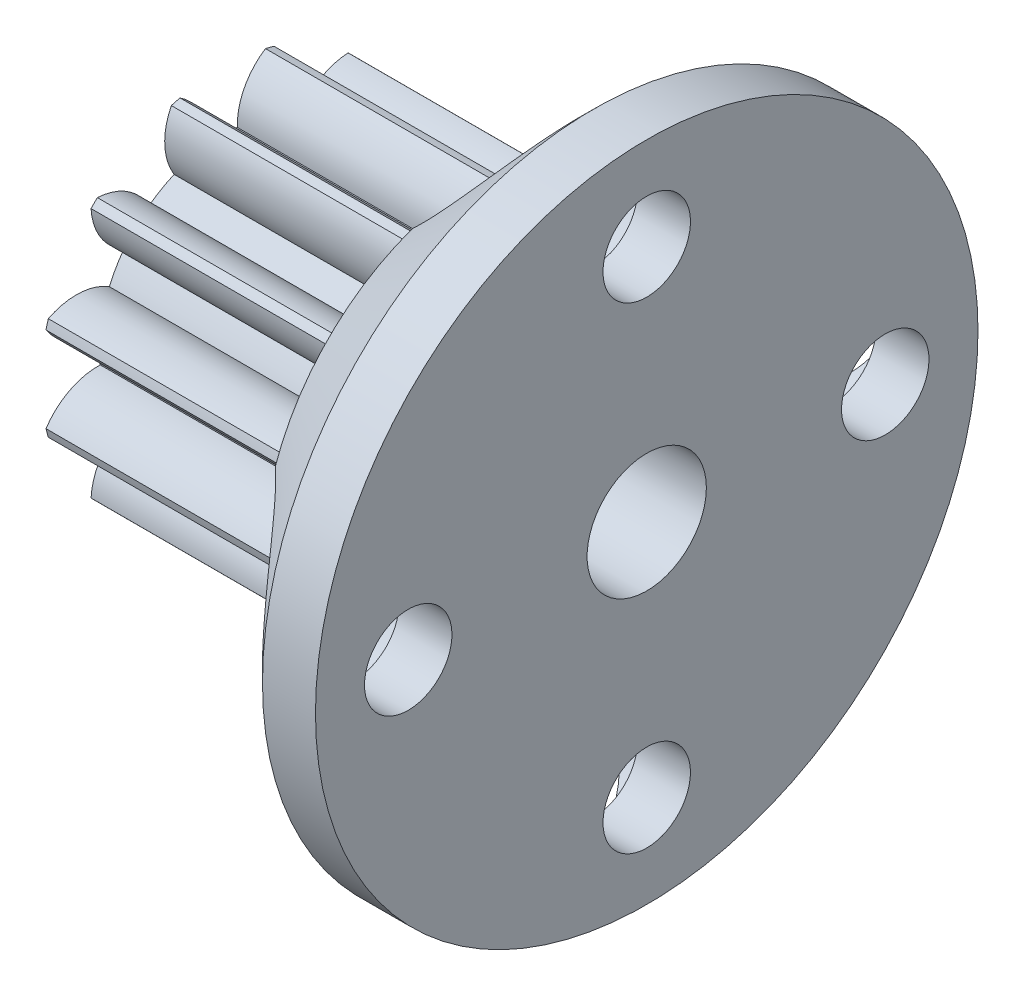
SolidWorks part; units mm, degrees
ref_plane "Plane1" through (0, 0, 0) normal (0, 0, 1) x (1, 0, 0)
ref_plane "Plane2" through (0, 0, 0) normal (0, 1, 0) x (1, 0, 0)
ref_plane "Plane3" through (0, 0, 0) normal (1, 0, 0) x (0, 0, -1)
other "Configuration Table"
sketch "HoldingSke" plane through (0, 0, 0) normal (0, 1, 0) x (1, 0, 0)
  line L0 (0, 0) -> (0.9981, -0.2122)
  line L1 (-15, 0) -> (100, 0) construction
  line L2 (0, 0) -> (-2.1039, 2.3779)
  line L3 (0, 0) -> (-11.863, 4.5341)
  line L4 (0, 0) -> (8.4473, 1.7955)
  line L5 (0, 0) -> (-46.8476, -17.4728)
  line L6 (0, 0) -> (-8.2896, -5.593)
  line L7 (-2.1039, 2.3779) -> (8.6586, 51.2059)
  line L8 (-76.2, 54.61) -> (-75.5, 54.61)
  line L9 (-71.009, 38.7566) -> (-53.1078, 45.2721)
  line L10 (-76.2, 71.12) -> (104.1128, 71.12)
  line L11 (0, 0) -> (-10, 0)
  line L12 (-76.2, 101.6) -> (-76.162, 101.6)
  line L13 (24.9733, 27.94) -> (52.9518, 28.4284)
  line L14 (24.9733, 27.94) -> (24.9743, 27.94)
  line L15 (24.9733, 27.94) -> (100.4006, 29.5858)
  line L16 (-63.627, -0.98) -> (-12.827, -0.98)
  circle A0 centre (0, 0) radius 1
  circle A1 centre (0, 0) radius 4.654
  circle A2 centre (0, 0) radius 37.5
  circle A3 centre (0, 0) radius 1
  dimension "Num_teeth" = 12
  dimension "Pitch_radius" = 180.3128
  dimension "Width" = 10
  dimension "Thickness" = 10
sketch "BasProSke" plane through (0, 0, 0) normal (0, 1, 0) x (1, 0, 0)
  line L0 (-10, 0) -> (60, 0) construction
  line L1 (0, 0) -> (0, 6.86)
  line L2 (0, 0) -> (10, 0)
  line L3 (10, 0) -> (10, 6.86)
  line L4 (10, 6.86) -> (0, 6.86)
  dimension "Thickness" = 10
  dimension "Diameter" = 13.72
revolve "Base-Revolve" add sketch "BasProSke" angle 360 about L0
sketch "TooCutSke" plane through (0, 0, 0) normal (1, 0, 0) x (0, 0, -1)
  line L1 (0, 0) -> (0, 107) construction
  line L2 (0, 0) -> (-0.8339, 5.8206) construction
  line L3 (0, 0) -> (-3.022, 11.2783) construction
  line L4 (-0.8339, 5.8206) -> (-1.511, 5.6391) construction
  arc A0 (0.552, 4.6211) -> (-0.552, 4.6211) centre (0, 0) ccw
  arc A1 (1.6415, 6.6869) -> (-1.6415, 6.6869) centre (0, 0) ccw
  circle A2 centre (0, 0) radius 5.88 construction
  circle A3 centre (0, 0) radius 5.5254 construction
  arc A4 (-0.552, 4.6211) -> (-1.6415, 6.6869) centre (-2.9026, 4.7016) ccw
  arc A5 (1.6415, 6.6869) -> (0.552, 4.6211) centre (2.9026, 4.7016) ccw
extrude "ToothCut" cut sketch "TooCutSke" along normal through all
fillet "Breaks" [suppressed] radius 0.0196 tangent propagation no
fillet "RootFillets" [suppressed] radius 0.246
pattern_circular "TeethCuts" count 12 every 30 about axis through (-10, 0, 0) along (1, 0, 0) of "ToothCut", "RootFillets", "Breaks"
sketch "HubNeaOneSke" plane through (0, 0, 0) normal (-1, 0, 0) x (0, 0, 1)
  circle A0 centre (0, 0) radius 4.654
  dimension "Diameter" = 9.308
extrude "HubNearOne" [suppressed] add sketch "HubNeaOneSke" along normal blind 40.0001
sketch "HubNeaBotSke" plane through (0, 0, 0) normal (-1, 0, 0) x (0, 0, 1)
  circle A0 centre (0, 0) radius 4.654
  dimension "Diameter" = 9.308
extrude "HubNearBoth" [suppressed] add sketch "HubNeaBotSke" along normal blind 20
ref_plane "FarPln" through (10, 0, 0) normal (1, 0, 0) x (0, 0, -1)
sketch "HubFarSke" plane through (10, 0, 0) normal (1, 0, 0) x (0, 0, -1)
  circle A0 centre (0, 0) radius 4.654
  dimension "Diameter" = 9.308
extrude "HubFar" [suppressed] add sketch "HubFarSke" along normal blind 20
sketch "BorSke" plane through (0, 0, 0) normal (1, 0, 0) x (0, 0, -1)
  circle A0 centre (0, 0) radius 1
  dimension "Diameter" = 2
extrude "Bore" cut sketch "BorSke" along normal mid plane 100.0001
sketch "KeySke" plane through (0, 0, 0) normal (1, 0, 0) x (0, 0, -1)
  line L0 (-0.8, 0) -> (-0.8, 1.7)
  line L1 (-0.8, 1.7) -> (0.8, 1.7)
  line L2 (0.8, 1.7) -> (0.8, 0)
  line L3 (0, 0) -> (0, 34) construction
  line L4 (-0.8, 0) -> (0.8, 0)
  dimension "Width" = 1.6
extrude "Keyway" [suppressed] cut sketch "KeySke" along normal mid plane 100.0001
pattern_circular "Keyway2" [suppressed] count 2 every 90 about axis through (-10, 0, 0) along (1, 0, 0)
sketch "Sketch1" plane through (10, 0, 0) normal (1, 0, 0) x (0, 0, -1)
  circle A0 centre (0, 0) radius 12.5
  dimension "D1" = 25
extrude "Boss-Extrude1" add sketch "Sketch1" along normal blind 6
sketch "Sketch2" plane through (10, 0, 0) normal (-1, 0, 0) x (0, 0, 1)
  circle A0 centre (0, 9) radius 1.65
  point P2 (0, 0)
  dimension "D1" = 3.3
  dimension "D2" = 9
extrude "Cut-Extrude1" cut sketch "Sketch2" against normal through all
sketch "Sketch3" plane through (10, 0, 0) normal (-1, 0, 0) x (0, 0, 1)
  circle A0 centre (0, 9) radius 3
  dimension "D1" = 6
extrude "Cut-Extrude2" cut sketch "Sketch3" against normal blind 4
pattern_circular "CirPattern1" count 4 over 360 about axis through (16, 0, 0) along (-1, 0, 0) of "Cut-Extrude1", "Cut-Extrude2" reverse direction yes
chamfer "Chamfer1" distance 4 angle 45 1 edges at (10, 0, -12.5)
sketch "Sketch4" plane through (16, 0, 0) normal (1, 0, 0) x (0, 0, -1)
  circle A0 centre (0, 0) radius 2.25
  dimension "D1" = 4.5
extrude "Cut-Extrude3" cut sketch "Sketch4" against normal blind 6
equation "' \"Module@HoldingSke\" = 6.35"
equation "' \"Num_teeth@HoldingSke\" = 12"
equation "' \"Ap@HoldingSke\" =  20"
equation "' \"Ap@HoldingSke\" = 20"
equation "' \"Width@HoldingSke\" = 0.5 * 25.4"
equation "' \"Hub_dia@HoldingSke\"= 1 * 25.4"
equation "' \"Hub_dia@HoldingSke\" = 1 * 25.4"
equation "' \"Overall_len@HoldingSke\" = 1.0 * 25.4"
equation "' \"Bore@HoldingSke\" = 0.75 * 25.4"
equation "' \"T_dim@HoldingSke\" = 0.1 * 25.4"
equation "' \"Width@KeySke\" = 0.25 * 25.4"
equation "' \"Show_teeth@HoldingSke\" = 13"
equation "' \"Backlash@HoldingSke\" = 0.009 * 25.4"
equation "' \"Addendum_fac@HoldingSke\" = 1.0"
equation "' \"Dedendum_fac@HoldingSke\" = 1.25"
equation "' \"Dedendum_add@HoldingSke\" = 0.00005 * 25.4"
equation "' \"Clearance_fac@HoldingSke\" = 0.25"
equation "\"Pitch@HoldingSke\" = 1 / \"Module@HoldingSke\""
equation "\"Overcut_dia@TooCutSke\" = (\"Num_teeth@HoldingSke\" + 2 * \"Addendum_fac@HoldingSke\") / \"Pitch@HoldingSke\" + 0.002 * 25.4"
equation "\"Pitch_dia@TooCutSke\" = \"Num_teeth@HoldingSke\" / \"Pitch@HoldingSke\""
equation "\"Base_dia@TooCutSke\" = \"Num_teeth@HoldingSke\" / \"Pitch@HoldingSke\" * cos((\"Ap@HoldingSke\"  * 3.14159265 / 180))"
equation "\"Root_dia@TooCutSke\" = (\"Num_teeth@HoldingSke\" + 2) / \"Pitch@HoldingSke\" - 2 * (\"Addendum_fac@HoldingSke\" + \"Dedendum_fac@HoldingSke\") / \"Pitch@HoldingSke\" - \"Dedendum_add@HoldingSke\" * 2"
equation "\"Half_ang@TooCutSke\" = 180 / \"Num_teeth@HoldingSke\""
equation "\"Half_CT@TooCutSke\" = \"Num_teeth@HoldingSke\" / \"Pitch@HoldingSke\" * sin((3.14159265 / 2 / \"Num_teeth@HoldingSke\")) / 2 - 7 * \"Backlash@HoldingSke\" / 4"
equation "\"Flank_rad@TooCutSke\" = \"Num_teeth@HoldingSke\" / \"Pitch@HoldingSke\" / 5"
equation "\"Radius@RootFillets\" = \"Clearance_fac@HoldingSke\" / \"Pitch@HoldingSke\" + \"Dedendum_add@HoldingSke\""
equation "\"Break_rad@Breaks\" = 0.02 / \"Pitch@HoldingSke\""
equation "\"Thickness@HoldingSke\" = \"Width@HoldingSke\""
equation "\"OAL@HoldingSke\" = \"Thickness@HoldingSke\""
equation "\"MHD@HoldingSke\" = (\"Num_teeth@HoldingSke\" + 2) / \"Pitch@HoldingSke\" - 2 * (\"Addendum_fac@HoldingSke\" + \"Dedendum_fac@HoldingSke\")  / \"Pitch@HoldingSke\" - \"Dedendum_add@HoldingSke\" * 2"
equation "\"MBD@HoldingSke\" = (\"Num_teeth@HoldingSke\" + 2) / \"Pitch@HoldingSke\" - 2 * (\"Addendum_fac@HoldingSke\" + \"Dedendum_fac@HoldingSke\")  / \"Pitch@HoldingSke\" - \"Dedendum_add@HoldingSke\" * 2 - 0.002 * 25.4"
equation "\"MHD@HoldingSke\" = ((sgn( \"MHD@HoldingSke\" - \"Hub_dia@HoldingSke\" )-1)*( \"MHD@HoldingSke\" - \"Hub_dia@HoldingSke\" ))/-2+ \"Hub_dia@HoldingSke\""
equation "\"MBD@HoldingSke\" = ((sgn( \"MBD@HoldingSke\" - \"Bore@HoldingSke\" )-1)*( \"MBD@HoldingSke\" - \"Bore@HoldingSke\" ))/-2+ \"Bore@HoldingSke\""
equation "\"OAL@HoldingSke\" = ((sgn( \"OAL@HoldingSke\" - \"Overall_len@HoldingSke\" )+1)*( \"OAL@HoldingSke\" - \"Overall_len@HoldingSke\" ))/2 + \"Overall_len@HoldingSke\" + 0.000002 * 25.4"
equation "\"Num_teeth@TeethCuts\" = int( \"Show_teeth@HoldingSke\" ) + 1"
equation "\"Num_teeth@TeethCuts\" = ((sgn( \"Num_teeth@TeethCuts\" - \"Num_teeth@HoldingSke\" )-1)*( \"Num_teeth@TeethCuts\" - \"Num_teeth@HoldingSke\" ))/-2+ \"Num_teeth@HoldingSke\""
equation "\"Num_teeth@TeethCuts\" = ((sgn( \"Num_teeth@TeethCuts\" - 2.0)+1)*( \"Num_teeth@TeethCuts\" - 2.0))/2 +2.0"
equation "\"Angle@TeethCuts\" = 360.0 / \"Num_teeth@HoldingSke\""
equation "\"Diameter@BasProSke\" = (\"Num_teeth@HoldingSke\" + 2 * \"Addendum_fac@HoldingSke\") / \"Pitch@HoldingSke\""
equation "\"Thickness@BasProSke\"  = \"Thickness@HoldingSke\""
equation "' \"Fillet_rad@BasProSke\" =  \"Thickness@HoldingSke\" * 0.05"
equation "' \"Fillet_rad@BasProSke\" = \"Thickness@HoldingSke\" * 0.05"
equation "\"MHD@HoldingSke\" = ((sgn( \"MHD@HoldingSke\" - \"Root_dia@TooCutSke\" )-1)*( \"MHD@HoldingSke\" - \"Root_dia@TooCutSke\" ))/-2+ \"Root_dia@TooCutSke\""
equation "\"Diameter@HubNeaOneSke\" = \"MHD@HoldingSke\""
equation "\"Length@HubNearOne\" = \"OAL@HoldingSke\" - \"Thickness@BasProSke\""
equation "\"Diameter@HubNeaBotSke\" = \"MHD@HoldingSke\""
equation "\"Length@HubNearBoth\" = ( \"OAL@HoldingSke\" - \"Thickness@BasProSke\" ) / 2.0"
equation "\"Thickness@FarPln\" = \"Thickness@BasProSke\""
equation "\"Diameter@HubFarSke\" = \"MHD@HoldingSke\""
equation "\"Length@HubFar\" = ( \"OAL@HoldingSke\" - \"Thickness@BasProSke\" ) / 2.0"
equation "\"Diameter@BorSke\" = \"MBD@HoldingSke\""
equation "\"D1@Bore\" = \"OAL@HoldingSke\" * 2.0"
equation "\"D1@Keyway\" = \"OAL@HoldingSke\" * 2.0"
equation "\"Offset@KeySke\" = \"T_dim@HoldingSke\" + \"MBD@HoldingSke\" / 2.0"
